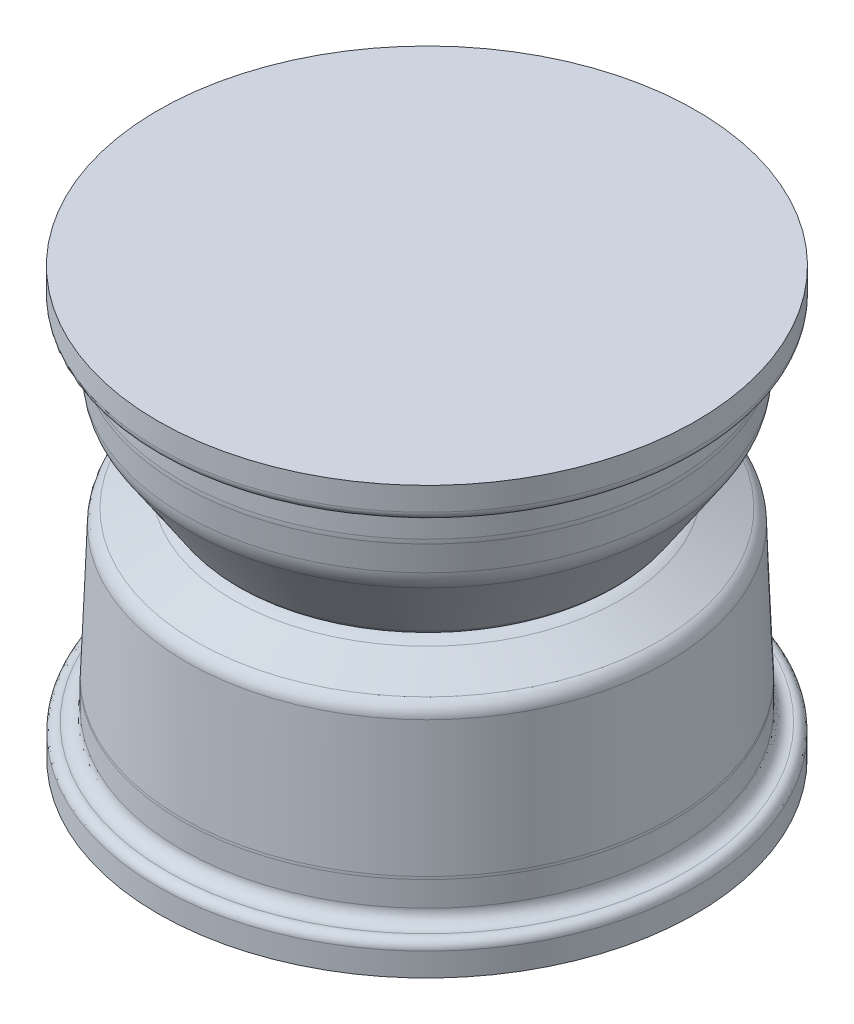
SolidWorks part; units mm, degrees
ref_plane "Ground Plane" through (0, 0, 0) normal (0, 0, 1) x (1, 0, 0)
ref_plane "Center Plane" through (0, 0, 0) normal (0, 1, 0) x (1, 0, 0)
ref_plane "Left Plane" through (0, 0, 0) normal (1, 0, 0) x (0, 0, -1)
ref_axis "FRONT (X)" through (88.99, 0, 0) along (-1, 0, 0)
ref_axis "LEFT (Y)" through (0, 55, 0) along (0, -1, 0)
ref_axis "UP (Z)" through (0, 0, 55) along (0, 0, -1)
sketch "Sketch1" plane through (0, 0, 0) normal (1, 0, 0) x (0, 0, -1)
  line L0 (-138.5553, 98.3653) -> (-138.5553, 110.3653)
  line L1 (-80.264, 13.0473) -> (0, 13.0473) construction
  line L2 (-91.7988, 13.0473) -> (-91.186, 13.0473)
  line L3 (-125.0363, -13.7764) -> (-125.0363, -64.6767) construction
  line L4 (0, 55) -> (0, -55) construction
  line L5 (0, 13.0473) -> (0, 0) construction
  line L6 (-91.186, 13.0473) -> (-80.264, 13.0473)
  line L7 (-125.1326, -66.8905) -> (-126.2061, -79.1971) construction
  line L8 (-138.4275, -97.4002) -> (-138.4275, -109.4002)
  line L9 (-126.3025, -81.4109) -> (-126.3025, -86.8372)
  line L10 (-126.3025, -81.4109) -> (-126.3025, -74.0829)
  line L11 (-126.3025, -73.4109) -> (-126.3025, -54.737) construction
  line L12 (-126.3025, -73.4109) -> (-125.6747, -57.0694) construction
  line L13 (-124.5614, -4.0239) -> (-125.0016, -12.4471) construction
  line L14 (-126.2767, -72.7393) -> (-123.6618, -4.6718)
  line L15 (-119.057, 2.2677) -> (-99.8255, 11.2625)
  line L16 (-138.4275, -109.4002) -> (0, -109.4002)
  line L17 (-138.5553, 110.3653) -> (0, 110.3653)
  line L18 (0, 110.3653) -> (0, -109.4002)
  line L20 (-122.2465, 53.1368) -> (-97.7832, 16.5711)
  line L24 (-126.5858, 75.7305) -> (-125.3906, 62.0693)
  line L27 (-126.6825, 87.5011) -> (-126.6825, 77.9443)
  arc A0 (-123.6618, -4.6718) -> (-119.057, 2.2677) centre (-115.6677, -4.9789) cw
  arc A1 (-126.3025, -74.0829) -> (-126.2767, -72.7393) centre (-91.3025, -74.0829) cw
  arc A3 (-125.1326, -66.8905) -> (-125.0363, -64.6767) centre (-150.5122, -64.6767) ccw construction
  arc A7 (-126.2061, -79.1971) -> (-126.3025, -81.4109) centre (-100.8265, -81.4108) ccw construction
  arc A11 (-125.0016, -12.4471) -> (-125.0363, -13.7764) centre (-99.56, -13.7764) ccw construction
  arc A15 (-97.7832, 16.5711) -> (-91.186, 13.0473) centre (-91.186, 20.9848) ccw
  arc A19 (-125.3906, 62.0693) -> (-122.2465, 53.1368) centre (-106.4131, 63.7296) ccw
  arc A23 (-126.6825, 77.9443) -> (-126.5858, 75.7305) centre (-101.2825, 77.9443) ccw
  arc A25 (-126.6825, 87.5011) -> (-133.6675, 93.8193) centre (-133.0325, 87.5011) ccw
  arc A29 (-138.5553, 98.3653) -> (-133.6675, 93.8193) centre (-134.112, 98.242) ccw
  arc A35 (-137.2648, 100.2011) -> (-138.5553, 98.3653) centre (-136.5241, 98.3089) ccw construction
  arc A39 (-129.4861, -96.8062) -> (-129.4256, -96.6408) centre (-131.6051, -95.9365) ccw construction
  arc A43 (-131.445, 98.8993) -> (-137.2648, 100.2011) centre (-135.3204, 95.2342) ccw construction
  arc A47 (-130.1099, 97.1057) -> (-131.445, 98.8993) centre (-138.3653, 92.3544) ccw construction
  arc A51 (-130.1099, 97.1057) -> (-129.0777, 96.1663) centre (-128.1286, 98.246) ccw construction
  arc A55 (-123.5075, 87.5011) -> (-129.0777, 96.1663) centre (-133.0325, 87.5011) ccw construction
  spline S1 degree 3 poles (-133.5197, -93.1247) (-128.8347, -93.7891) (-126.3025, -90.3595) (-126.3025, -86.8372) knots 0 0 0 0 1 1 1 1 weights 0.255592 0.242825 0.327183 0.508666
  spline S5 degree 3 poles (-133.5197, -93.1247) (-136.7056, -92.6729) (-138.4275, -95.0051) (-138.4275, -97.4002) knots 0 0 0 0 1 1 1 1 weights 0.255592 0.242825 0.327183 0.508666
  spline S9 degree 3 poles (-138.4275, -97.4002) (-138.4275, -97.9754) (-138.1933, -98.5846) (-137.631, -99.0152) knots 0 0 0 0 1 1 1 1 weights 0.508666 0.39644 0.321354 0.283409 construction
  spline S13 degree 3 poles (-120.9147, 1.3988) (-123.3199, 0.2738) (-124.4499, -1.8895) (-124.5614, -4.0239) knots 0 0 0 0 1 1 1 1 weights 0.266833 0.294171 0.366349 0.483369 construction
  spline S17 degree 3 poles (-91.7988, 13.0473) (-94.6059, 13.0473) (-97.3224, 12.4332) (-99.8255, 11.2625) knots 0 0 0 0 1 1 1 1 weights 0.254333 0.254333 0.2585 0.266833
  spline S21 degree 3 poles (-137.631, -99.0152) (-134.4296, -101.4669) (-130.8483, -100.1251) (-129.4861, -96.8062) knots 0 0 0 0 1 1 1 1 weights 0.283409 0.225628 0.253966 0.36842 construction
  spline S25 degree 3 poles (-128.298, -95.3117) (-128.8755, -95.6089) (-129.2497, -96.0965) (-129.4256, -96.6408) knots 0 0 0 0 1 1 1 1 weights 0.269177 0.289066 0.328939 0.388797 construction
  spline S29 degree 3 poles (-128.298, -95.3117) (-124.6793, -93.4493) (-123.137, -90.0599) (-123.137, -86.8372) knots 0 0 0 0 1 1 1 1 weights 0.269177 0.300244 0.380074 0.508666 construction
  dimension "D4" = 8
  dimension "D5" = 35
  dimension "D1" = 12
  dimension "D2" = 8
  dimension "D3" = 2.2
  dimension "D6" = 12
sketch "Sketch2" plane through (0, 0, 0) normal (0, 1, 0) x (1, 0, 0)
  line L0 (82.804, 22.1873) -> (-82.804, -22.1873) construction
  line L1 (0, 0) -> (-62.4463, 0) construction
  line L2 (88.99, 0) -> (-88.99, 0) construction
  circle A0 centre (-82.804, -22.1873) radius 3.175
  circle A1 centre (-82.804, 22.1873) radius 3.175
  circle A2 centre (-60.6167, 60.6167) radius 3.175
  circle A3 centre (-22.1873, 82.804) radius 3.175
  circle A4 centre (22.1873, 82.804) radius 3.175
  circle A5 centre (60.6167, 60.6167) radius 3.175
  circle A6 centre (82.804, 22.1873) radius 3.175
  circle A7 centre (82.804, -22.1873) radius 3.175
  circle A8 centre (60.6167, -60.6167) radius 3.175
  circle A9 centre (22.1873, -82.804) radius 3.175
  circle A10 centre (-22.1873, -82.804) radius 3.175
  circle A11 centre (-60.6167, -60.6167) radius 3.175
  point P6 (0, 0)
  point P34 (0, 0)
  dimension "D3" = 6.35
  dimension "D1" = 171.45
  dimension "D2" = 15
  dimension "D4" = 12
revolve "Revolve1" add sketch "Sketch1" angle 360 about axis through (0, 55, 0) along (0, -1, 0)
